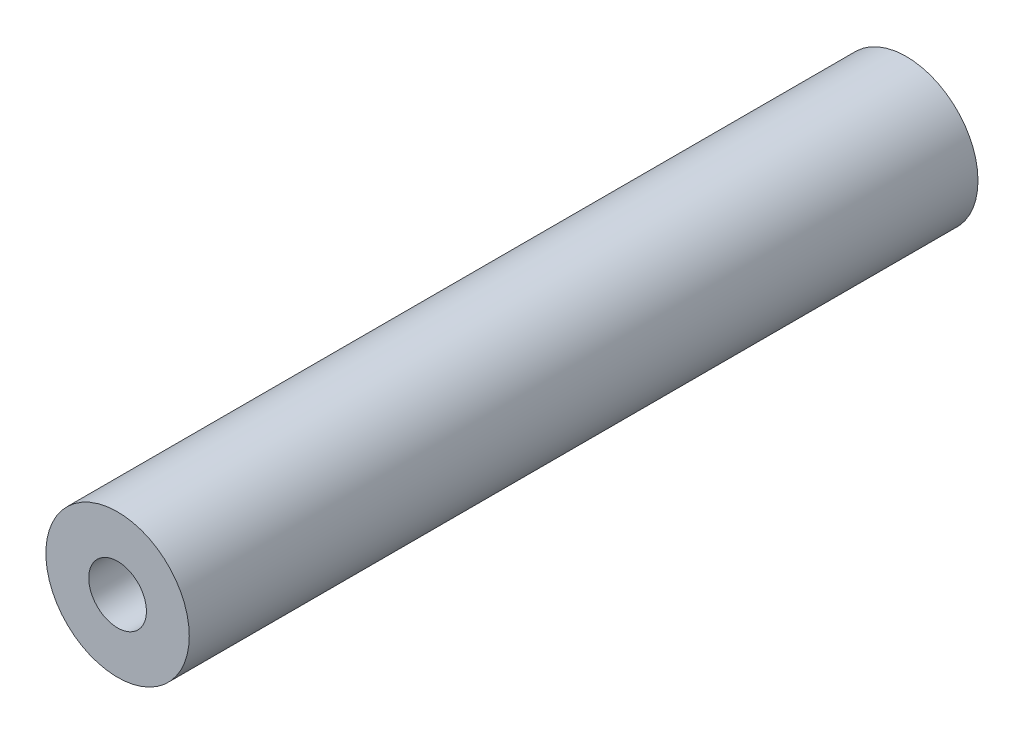
SolidWorks part; units mm, degrees
ref_plane "Ebene vorne" through (0, 0, 0) normal (0, 0, 1) x (1, 0, 0)
ref_plane "Ebene oben" through (0, 0, 0) normal (0, 1, 0) x (1, 0, 0)
ref_plane "Ebene rechts" through (0, 0, 0) normal (1, 0, 0) x (0, 0, -1)
sketch "Skizze1" plane through (0, 0, 0) normal (0, 0, 1) x (1, 0, 0)
  circle A0 centre (0, 0) radius 10
  circle A1 centre (0, 0) radius 4.025
  dimension "D1" = 20
  dimension "D2" = 8.05
extrude "Aufsatz-Linear austragen1" add sketch "Skizze1" along normal blind 110
ref_axis "Achse1" through (0, 0, 110) along (0, 0, -1)
